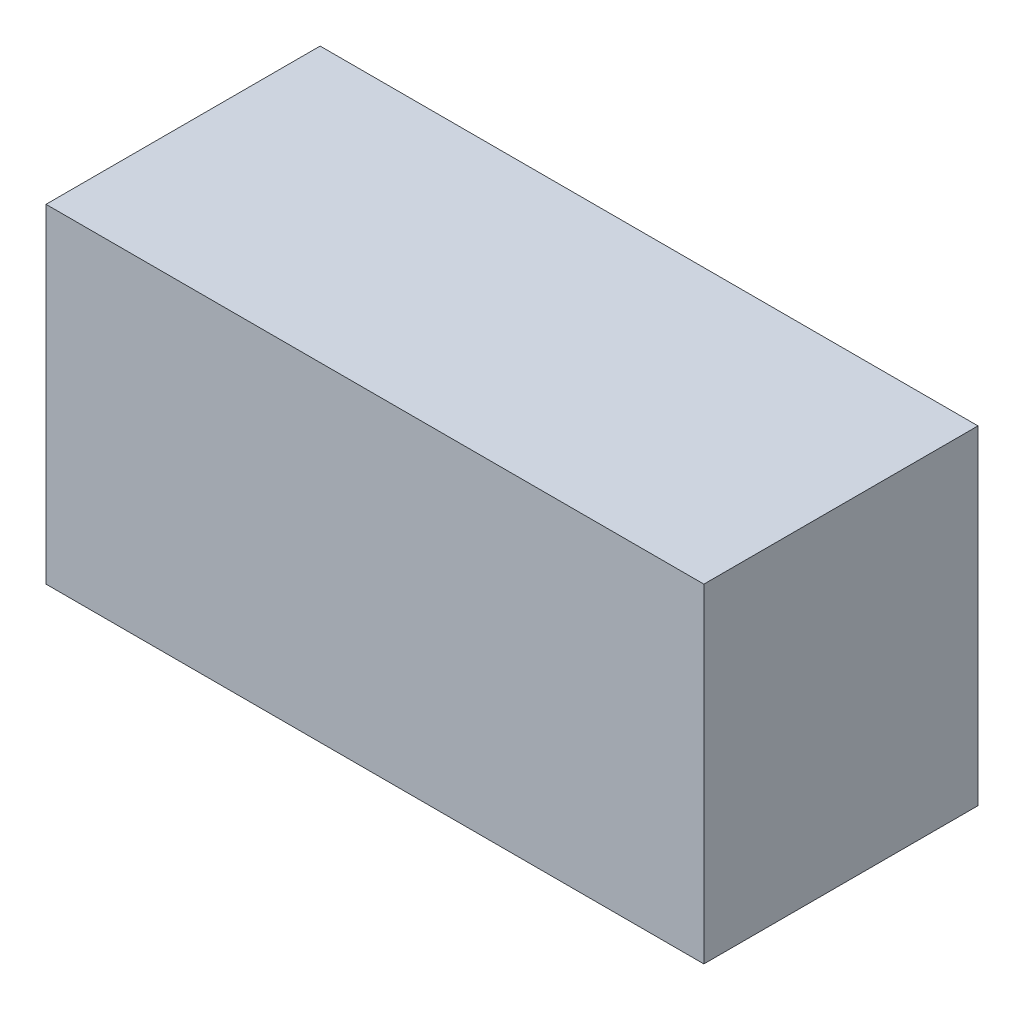
SolidWorks part; units mm, degrees
ref_plane "Front Plane" through (0, 0, 0) normal (0, 0, 1) x (1, 0, 0)
ref_plane "Top Plane" through (0, 0, 0) normal (0, 1, 0) x (1, 0, 0)
ref_plane "Right Plane" through (0, 0, 0) normal (1, 0, 0) x (0, 0, -1)
sketch "Sketch1" plane through (0, 0, 0) normal (1, 0, 0) x (0, 0, -1)
  line L1 (0, 0) -> (125, 0)
  line L2 (0, 0) -> (0, 150)
  line L3 (0, 150) -> (125, 150)
  line L4 (125, 0) -> (125, 150)
  dimension "D1" = 125
  dimension "D2" = 150
extrude "Boss-Extrude1" add sketch "Sketch1" along normal blind 300
equation "\"length\"= 300"
equation "\"height\"=150"
equation "\"D1@Sketch1\"=\"width\""
equation "\"width\"=125"
equation "\"D2@Sketch1\"=\"height\""
equation "\"D1@Boss-Extrude1\"=\"length\""
